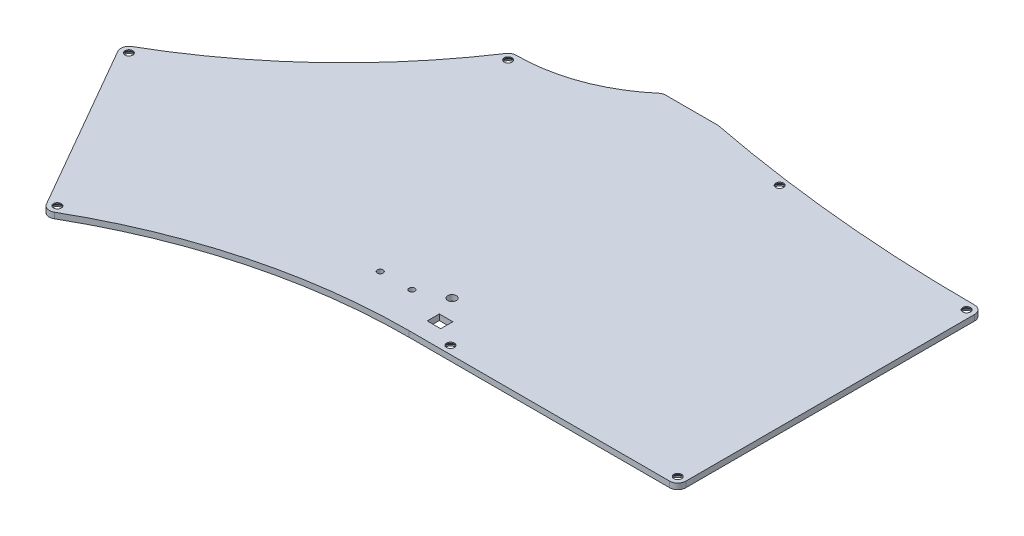
SolidWorks part; units mm, degrees
ref_plane "Front Plane" through (0, 0, 0) normal (0, 0, 1) x (1, 0, 0)
ref_plane "Top Plane" through (0, 0, 0) normal (0, 1, 0) x (1, 0, 0)
ref_plane "Right Plane" through (0, 0, 0) normal (1, 0, 0) x (0, 0, -1)
sketch "Main_line" plane through (0, 0, 0) normal (0, 1, 0) x (1, 0, 0)
  line L5 (53.3323, -110.4715) -> (58.0323, -110.4715) construction
  line L6 (53.3323, -110.4715) -> (53.3323, -114.6715) construction
  line L7 (53.3323, -114.6715) -> (58.0323, -114.6715) construction
  line L8 (58.0323, -110.4715) -> (58.0323, -114.6715) construction
  line L12 (53.5323, -110.5715) -> (57.8323, -110.5715) construction
  line L13 (57.9323, -110.6715) -> (57.9323, -114.4715) construction
  line L14 (53.4323, -114.4715) -> (53.4323, -110.6715) construction
  line L15 (57.8323, -114.5715) -> (53.5323, -114.5715) construction
  line L57 (53.0696, -120.9715) -> (143.7823, -120.9715)
  line L58 (-81.9059, -87.3079) -> (-48.2619, -145.8257)
  line L59 (44.7823, -4.9715) -> (26.7823, -4.9715)
  line L60 (146.7823, -117.9715) -> (146.7823, -17.4715)
  line L61 (53.0696, -120.9715) -> (143.7823, -120.9715) construction
  line L62 (-81.9059, -87.3079) -> (-48.2619, -145.8257) construction
  line L63 (44.7823, -4.9715) -> (26.7823, -4.9715) construction
  line L64 (146.7823, -117.9715) -> (146.7823, -17.4715) construction
  circle A0 centre (50.7823, -103.4715) radius 1.5 construction
  circle A1 centre (41.2823, -107.9515) radius 1 construction
  circle A2 centre (30.2823, -107.9515) radius 1 construction
  circle A3 centre (-79.3051, -85.8126) radius 1.35 construction
  circle A4 centre (-11.2177, -21.9715) radius 1.35 construction
  circle A5 centre (50.7823, -103.4715) radius 1.5 construction
  arc A121 (143.7823, -120.9715) -> (146.7823, -117.9715) centre (143.7823, -117.9715) ccw
  arc A122 (53.0696, -120.9715) -> (-44.1658, -146.9312) centre (53.0696, -316.055) ccw
  arc A123 (-48.2619, -145.8257) -> (-44.1658, -146.9312) centre (-45.6611, -144.3304) ccw
  arc A124 (-80.8004, -83.2119) -> (-81.9059, -87.3079) centre (-79.3051, -85.8126) ccw
  arc A125 (-80.8004, -83.2119) -> (-13.717, -20.312) centre (-180.7133, 90.5689) ccw
  arc A126 (-11.2177, -18.9715) -> (-13.717, -20.312) centre (-11.2177, -21.9715) ccw
  arc A127 (-11.2177, -18.9715) -> (24.8359, -5.6886) centre (-11.2177, 36.5999) ccw
  arc A128 (26.7823, -4.9715) -> (24.8359, -5.6886) centre (26.7823, -7.9715) ccw
  arc A129 (45.3528, -5.0262) -> (44.7823, -4.9715) centre (44.7823, -7.9715) ccw
  arc A130 (45.3528, -5.0262) -> (143.7823, -14.4715) centre (143.7823, 503.1206) ccw
  arc A131 (146.7823, -17.4715) -> (143.7823, -14.4715) centre (143.7823, -17.4715) ccw
  arc A132 (143.7823, -120.9715) -> (146.7823, -117.9715) centre (143.7823, -117.9715) ccw construction
  arc A133 (53.0696, -120.9715) -> (-44.1658, -146.9312) centre (53.0696, -316.055) ccw construction
  arc A134 (-48.2619, -145.8257) -> (-44.1658, -146.9312) centre (-45.6611, -144.3304) ccw construction
  circle A146 centre (143.7823, -117.9715) radius 1.35 construction
  circle A147 centre (143.7823, -117.9715) radius 1.35 construction
  circle A148 centre (64.7207, -117.9715) radius 1.35 construction
  circle A149 centre (-45.6611, -144.3304) radius 1.35 construction
  circle A150 centre (-79.3051, -85.8126) radius 1.35 construction
  circle A151 centre (-11.2177, -21.9715) radius 1.35 construction
  circle A152 centre (73.7823, -12.5168) radius 1.35 construction
  circle A153 centre (143.7823, -17.4715) radius 1.35 construction
  arc A154 (-80.8004, -83.2119) -> (-81.9059, -87.3079) centre (-79.3051, -85.8126) ccw construction
  arc A155 (-80.8004, -83.2119) -> (-13.717, -20.312) centre (-180.7133, 90.5689) ccw construction
  arc A156 (-11.2177, -18.9715) -> (-13.717, -20.312) centre (-11.2177, -21.9715) ccw construction
  arc A157 (-11.2177, -18.9715) -> (24.8359, -5.6886) centre (-11.2177, 36.5999) ccw construction
  arc A158 (26.7823, -4.9715) -> (24.8359, -5.6886) centre (26.7823, -7.9715) ccw construction
  arc A159 (45.3528, -5.0262) -> (44.7823, -4.9715) centre (44.7823, -7.9715) ccw construction
  arc A160 (45.3528, -5.0262) -> (143.7823, -14.4715) centre (143.7823, 503.1206) ccw construction
  arc A161 (146.7823, -17.4715) -> (143.7823, -14.4715) centre (143.7823, -17.4715) ccw construction
  dimension "D2" = 2
  dimension "D3" = 0.1
  dimension "D4" = 3
  dimension "D5" = 0.1
  dimension "D6" = 0.1
  dimension "D7" = 0.1
  dimension "D1" = 0
sketch "Sketch1" plane through (0, 0, 0) normal (0, 1, 0) x (1, 0, 0)
  line L33 (-81.7325, -87.2082) -> (-48.0885, -145.726)
  line L34 (53.0696, -120.7715) -> (143.7823, -120.7715)
  line L35 (146.5823, -117.9715) -> (146.5823, -17.4715)
  line L36 (44.7823, -5.1715) -> (26.7823, -5.1715)
  line L37 (-81.7325, -87.2082) -> (-48.0885, -145.726)
  line L38 (53.0696, -120.7715) -> (143.7823, -120.7715)
  line L39 (146.5823, -117.9715) -> (146.5823, -17.4715)
  line L40 (44.7823, -5.1715) -> (26.7823, -5.1715)
  circle A93 centre (143.7823, -17.4715) radius 1.35
  circle A94 centre (143.7823, -17.4715) radius 1.35 construction
  circle A95 centre (73.7823, -12.5168) radius 1.35
  circle A96 centre (-11.2177, -21.9715) radius 1.35
  circle A97 centre (-79.3051, -85.8126) radius 1.35
  circle A98 centre (-45.6611, -144.3304) radius 1.35
  circle A99 centre (64.7207, -117.9715) radius 1.35
  circle A100 centre (143.7823, -117.9715) radius 1.35
  arc A139 (-80.7007, -83.3852) -> (-81.7325, -87.2082) centre (-79.3051, -85.8126) ccw
  arc A140 (-48.0885, -145.726) -> (-44.2655, -146.7578) centre (-45.6611, -144.3304) ccw
  arc A141 (53.0696, -120.7715) -> (-44.2655, -146.7578) centre (53.0696, -316.055) ccw
  arc A142 (143.7823, -120.7715) -> (146.5823, -117.9715) centre (143.7823, -117.9715) ccw
  arc A143 (146.5823, -17.4715) -> (143.7823, -14.6715) centre (143.7823, -17.4715) ccw
  arc A144 (45.3147, -5.2226) -> (143.7823, -14.6715) centre (143.7823, 503.1206) ccw
  arc A145 (45.3147, -5.2226) -> (44.7823, -5.1715) centre (44.7823, -7.9715) ccw
  arc A146 (26.7823, -5.1715) -> (24.9657, -5.8408) centre (26.7823, -7.9715) ccw
  arc A147 (-11.2177, -19.1715) -> (24.9657, -5.8408) centre (-11.2177, 36.5999) ccw
  arc A148 (-11.2177, -19.1715) -> (-13.5504, -20.4227) centre (-11.2177, -21.9715) ccw
  arc A149 (-80.7007, -83.3852) -> (-13.5504, -20.4227) centre (-180.7133, 90.5689) ccw
  arc A150 (-80.7007, -83.3852) -> (-81.7325, -87.2082) centre (-79.3051, -85.8126) ccw
  arc A151 (-48.0885, -145.726) -> (-44.2655, -146.7578) centre (-45.6611, -144.3304) ccw
  arc A152 (53.0696, -120.7715) -> (-44.2655, -146.7578) centre (53.0696, -316.055) ccw
  arc A153 (143.7823, -120.7715) -> (146.5823, -117.9715) centre (143.7823, -117.9715) ccw
  arc A154 (146.5823, -17.4715) -> (143.7823, -14.6715) centre (143.7823, -17.4715) ccw
  arc A155 (45.3147, -5.2226) -> (143.7823, -14.6715) centre (143.7823, 503.1206) ccw
  arc A156 (45.3147, -5.2226) -> (44.7823, -5.1715) centre (44.7823, -7.9715) ccw
  arc A157 (26.7823, -5.1715) -> (24.9657, -5.8408) centre (26.7823, -7.9715) ccw
  arc A158 (-11.2177, -19.1715) -> (24.9657, -5.8408) centre (-11.2177, 36.5999) ccw
  arc A159 (-11.2177, -19.1715) -> (-13.5504, -20.4227) centre (-11.2177, -21.9715) ccw
  arc A160 (-80.7007, -83.3852) -> (-13.5504, -20.4227) centre (-180.7133, 90.5689) ccw
  dimension "D1" = 0.2
extrude "Main_plate" add sketch "Sketch1" along normal blind 2
sketch "Sketch2" plane through (0, 0, 0) normal (0, -1, 0) x (1, 0, 0)
  circle A0 centre (143.7823, 117.9715) radius 2.5
  circle A1 centre (64.7207, 117.9715) radius 2.5
  circle A2 centre (-45.6611, 144.3304) radius 2.5
  circle A3 centre (-79.3051, 85.8126) radius 2.5
  circle A4 centre (-11.2177, 21.9715) radius 2.5
  circle A5 centre (73.7823, 12.5168) radius 2.5
  circle A6 centre (143.7823, 17.4715) radius 2.5
  dimension "D1" = 5
extrude "Cut-Extrude1" cut sketch "Sketch2" against normal blind 1.7
chamfer "Chamfer1" distance 1.2 angle 45 7 edges at (143.7823, 1.7, 14.9715) (73.7823, 1.7, 10.0168) (-11.2177, 1.7, 19.4715) (-79.3051, 1.7, 83.3126) (-45.6611, 1.7, 141.8304) (64.7207, 1.7, 115.4715) (143.7823, 1.7, 115.4715)
sketch "Sketch3" plane through (0, 0, 0) normal (0, -1, 0) x (1, 0, 0)
  circle A0 centre (41.2823, 107.9515) radius 1
  circle A1 centre (30.2823, 107.9515) radius 1
  circle A2 centre (41.2823, 107.9515) radius 1 construction
extrude "Led_hole" cut sketch "Sketch3" against normal through all
sketch "Sketch4" plane through (0, 0, 0) normal (0, -1, 0) x (1, 0, 0)
  line L1 (53.3323, 114.6715) -> (58.0323, 114.6715)
  line L2 (53.3323, 114.6715) -> (53.3323, 110.4715)
  line L3 (53.3323, 110.4715) -> (58.0323, 110.4715)
  line L4 (58.0323, 114.6715) -> (58.0323, 110.4715)
extrude "Main_switch_hole" cut sketch "Sketch4" against normal through all
sketch "Sketch5" plane through (0, 0, 0) normal (0, -1, 0) x (1, 0, 0)
  circle A0 centre (50.7823, 103.4715) radius 1.5
  circle A1 centre (50.7823, 103.4715) radius 1.5 construction
extrude "Reset_hole" cut sketch "Sketch5" against normal through all
